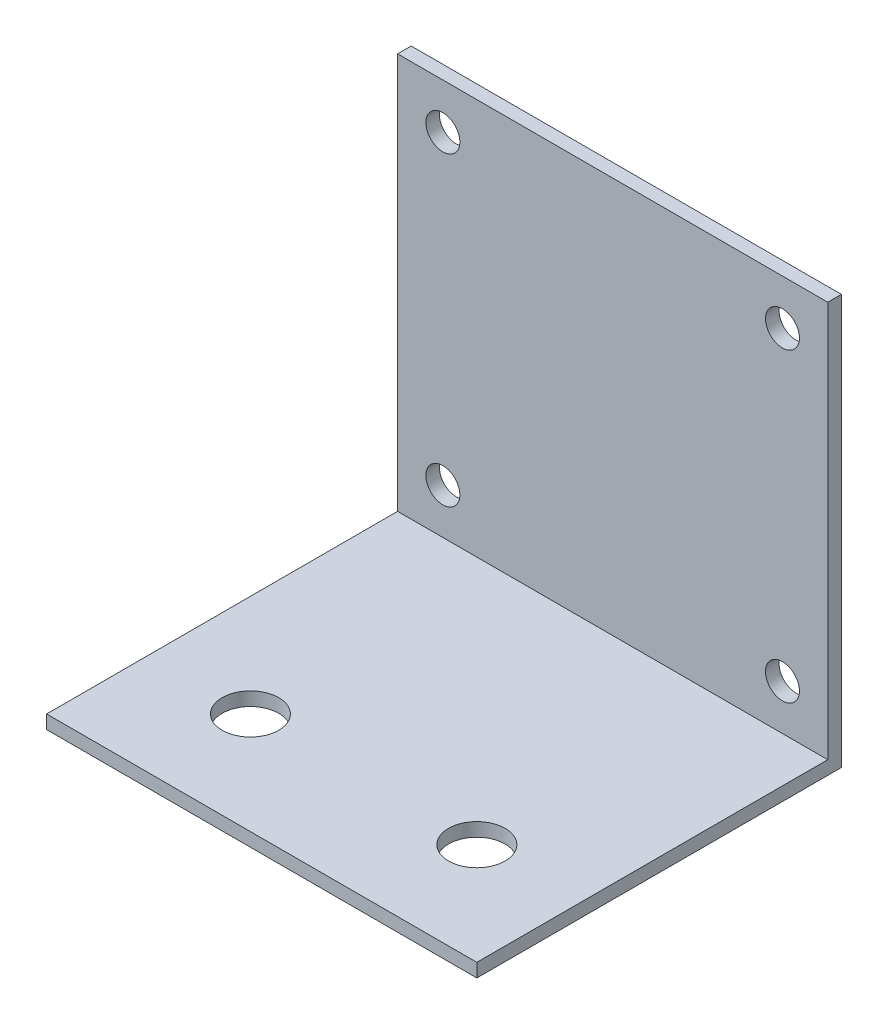
SolidWorks part; units mm, degrees
ref_plane "Front Plane" through (0, 0, 0) normal (0, 0, 1) x (1, 0, 0)
ref_plane "Top Plane" through (0, 0, 0) normal (0, 1, 0) x (1, 0, 0)
ref_plane "Right Plane" through (0, 0, 0) normal (1, 0, 0) x (0, 0, -1)
sketch "Sketch1" plane through (0, 0, 0) normal (0, 1, 0) x (1, 0, 0)
  line L0 (-19, 0) -> (-19, -32.2) construction
  line L1 (0, 0) -> (-38, 0)
  line L2 (0, 0) -> (0, -32.2)
  line L3 (0, -32.2) -> (-38, -32.2)
  line L4 (-38, 0) -> (-38, -32.2)
  circle A0 centre (-29, -23.2) radius 2.5
  circle A2 centre (-9, -23.2) radius 2.5
  dimension "D3" = 5
  dimension "D4" = 9
  dimension "D5" = 10
  dimension "D6" = 9
  dimension "D1" = 32.2
  dimension "D2" = 38
extrude "Boss-Extrude1" add sketch "Sketch1" along normal blind 1.2
sketch "Sketch2" plane through (0, 1.2, 0) normal (0, 1, 0) x (1, 0, 0)
  line L0 (0, -32.2) -> (0, 0) construction
  line L1 (-38, 0) -> (0, 0)
  line L2 (-38, 0) -> (-38, -1.2)
  line L3 (-38, -1.2) -> (0, -1.2)
  line L4 (0, 0) -> (0, -1.2)
  dimension "D1" = 1.2
extrude "Boss-Extrude2" add sketch "Sketch2" along normal blind 35
sketch "Sketch3" plane through (0, 0, 1.2) normal (0, 0, 1) x (1, 0, 0)
  line L0 (-19, 36.2) -> (-19, 1.2) construction
  line L1 (-38, 36.2) -> (0, 36.2) construction
  line L2 (-38, 1.2) -> (0, 1.2) construction
  line L3 (-38, 1.2) -> (0, 1.2) construction
  line L4 (-38, 36.2) -> (-38, 1.2) construction
  circle A0 centre (-34, 5.2) radius 1.5
  circle A1 centre (-34, 32.2) radius 1.5
  circle A2 centre (-4, 5.2) radius 1.5
  circle A3 centre (-4, 32.2) radius 1.5
  dimension "D1" = 4
  dimension "D2" = 4
  dimension "D3" = 4
  dimension "D4" = 3
  dimension "D5" = 4
  dimension "D6" = 3
extrude "Cut-Extrude1" cut sketch "Sketch3" against normal through all
